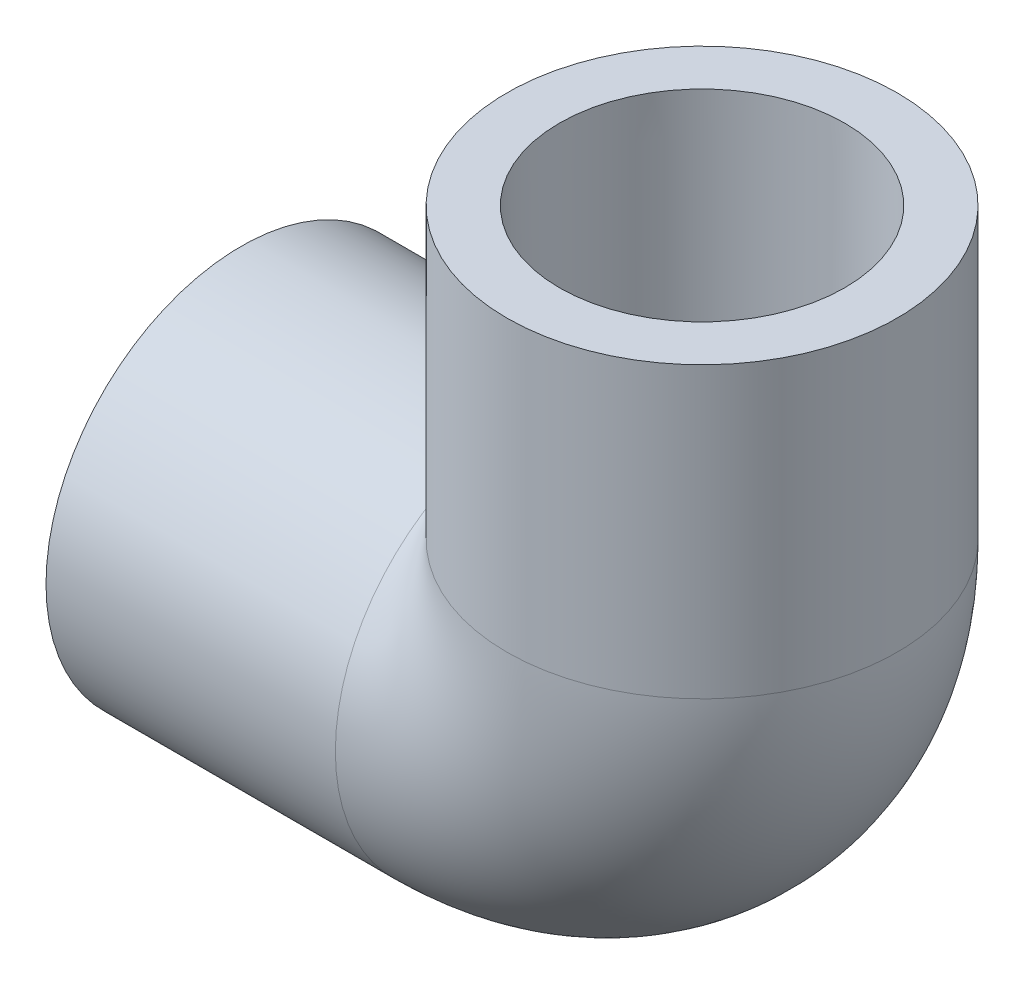
SolidWorks part; units mm, degrees
ref_plane "Front Plane" through (0, 0, 0) normal (0, 0, 1) x (1, 0, 0)
ref_plane "Top Plane" through (0, 0, 0) normal (0, 1, 0) x (1, 0, 0)
ref_plane "Right Plane" through (0, 0, 0) normal (1, 0, 0) x (0, 0, -1)
sketch "Sketch0" plane through (0, 0, 0) normal (0, 0, 1) x (1, 0, 0)
  line L0 (-34.798, 0) -> (0, 0) construction
  line L1 (0, 0) -> (0, 34.798) construction
  line L2 (-12.954, 0) -> (0, 0) construction
  line L3 (0, 0) -> (0, 12.954) construction
  line L4 (-34.798, 14.732) -> (-34.798, -14.732) construction
  line L5 (-12.954, 10.6172) -> (-34.798, 10.7696) construction
  line L6 (-12.954, 10.6172) -> (-12.954, -10.6172) construction
  line L7 (-12.954, -10.6172) -> (-34.798, -10.7696) construction
  line L8 (-34.798, 10.7696) -> (-34.798, -10.7696) construction
  line L9 (-14.732, 34.798) -> (14.732, 34.798) construction
  line L10 (-10.7696, 34.798) -> (10.7696, 34.798) construction
  line L11 (10.7696, 34.798) -> (10.6172, 12.954) construction
  line L12 (10.6172, 12.954) -> (-10.6172, 12.954) construction
  line L13 (-10.6172, 12.954) -> (-10.7696, 34.798) construction
  line L14 (-12.954, 6.9342) -> (-12.954, -6.9342) construction
  line L18 (-6.9342, 12.954) -> (6.9342, 12.954) construction
  dimension "H" = 34.798
  dimension "G" = 12.954
  dimension "M" = 29.464
  dimension "OD A" = 21.5392
  dimension "OD B" = 21.2344
  dimension "ID" = 13.8684
sketch "Sketch1" plane through (0, 0, 0) normal (0, 0, 1) x (1, 0, 0)
  line L0 (-34.798, 0) -> (0, 0) construction
  line L1 (-34.798, 0) -> (0, 0) construction
  line L3 (-34.798, -14.732) -> (-12.954, -14.732)
  line L4 (-34.798, -14.732) -> (-34.798, -10.7696)
  line L5 (-34.798, -10.7696) -> (-12.954, -10.6172)
  line L6 (-12.954, -14.732) -> (-12.954, -10.6172)
revolve "Revolve1" add sketch "Sketch1" angle 360 about L1
sketch "Sketch2" plane through (0, 0, 0) normal (0, 0, 1) x (1, 0, 0)
  line L0 (10.7696, 34.798) -> (10.6172, 12.954)
  line L1 (10.6172, 12.954) -> (14.732, 12.954)
  line L2 (14.732, 12.954) -> (14.732, 34.798)
  line L3 (14.732, 34.798) -> (10.7696, 34.798)
  line L4 (0, 0) -> (0, 34.798) construction
  line L5 (0, 0) -> (0, 34.798) construction
revolve "Revolve2" add sketch "Sketch2" angle 360 about L5
sketch "Sketch3" plane through (-12.954, 0, 0) normal (1, 0, 0) x (0, 0, -1)
  circle A0 centre (0, 0) radius 6.9342
  circle A1 centre (0, 0) radius 14.732
sketch "Sketch4" plane through (0, 0, 0) normal (0, 0, 1) x (1, 0, 0)
  line L0 (-34.798, 0) -> (0, 0) construction
  line L1 (0, 0) -> (0, 34.798) construction
  line L2 (-34.798, 0) -> (-12.954, 0) construction
  line L3 (0, 12.954) -> (0, 34.798) construction
  arc A0 (-12.954, 0) -> (0, 12.954) centre (-12.954, 12.954) ccw
sweep "Sweep1" add profiles "Sketch3" path "Sketch4"
other "CPoint1" parameters "Diameter"=12.7, "StubLength"=38.1
ref_axis "Axis1" through (0, 22.954, 0) along (0, -1, 0)
other "CPoint2" parameters "Diameter"=12.7, "StubLength"=38.1
ref_axis "Axis2" through (-22.954, 0, 0) along (1, 0, 0)
other "RPoint1"
